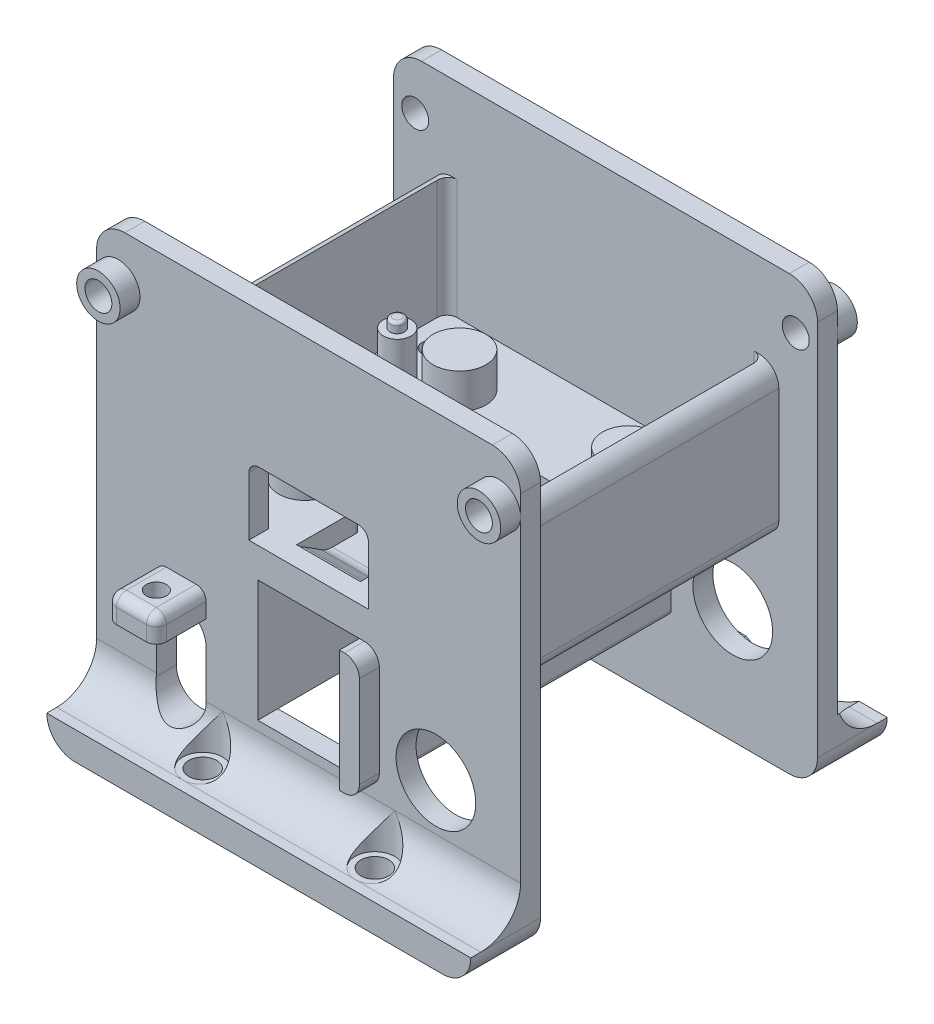
SolidWorks part; units mm, degrees
other "标注1"
sketch "草图55" plane through (-21.28, -20, 20.9) normal (0, 0, 1) x (1, 0, 0)
material "尼龙 101"
ref_plane "前视基准面" through (0, 0, 0) normal (0, 0, 1) x (1, 0, 0)
ref_plane "上视基准面" through (0, 0, 0) normal (0, 1, 0) x (1, 0, 0)
ref_plane "右视基准面" through (0, 0, 0) normal (1, 0, 0) x (0, 0, -1)
other "Configuration Table"
sketch "草图1" plane through (0, 0, 0) normal (0, 1, 0) x (1, 0, 0)
  line L1 (-15.9, 13.9) -> (15.9, 13.9)
  line L2 (-15.9, 13.9) -> (-15.9, -13.9)
  line L3 (-15.9, -13.9) -> (15.9, -13.9)
  line L4 (15.9, 13.9) -> (15.9, -13.9)
  line L5 (-15.9, 13.9) -> (15.9, -13.9) construction
  line L6 (-15.9, -13.9) -> (15.9, 13.9) construction
  point P0 (0, 0)
  dimension "D1" = 31.8
  dimension "D2" = 27.8
extrude "凸台-拉伸1" add sketch "草图1" along normal blind 3
sketch "草图2" plane through (0, 3, 0) normal (0, 1, 0) x (1, 0, 0)
  line L0 (0, 0) -> (0, 5.35) construction
  line L1 (-5.35, 5.35) -> (5.35, 5.35)
  line L2 (5.35, 5.35) -> (5.35, -7.55)
  line L3 (5.35, -7.55) -> (4.35, -7.55)
  line L4 (4.35, -7.55) -> (4.35, 4.35)
  line L5 (4.35, 4.35) -> (-4.35, 4.35)
  line L6 (-4.35, -7.55) -> (-4.35, 4.35)
  line L7 (-5.35, -7.55) -> (-4.35, -7.55)
  line L8 (-5.35, 5.35) -> (-5.35, -7.55)
  point P9 (0, 4.35)
  dimension "D1" = 8.7
  dimension "D2" = 11.9
  dimension "D3" = 4.35
  dimension "D4" = 1
  dimension "D5" = 1
extrude "凸台-拉伸2" add sketch "草图2" along normal blind 1.5
sketch "草图5" plane through (0, 3, 0) normal (0, 1, 0) x (1, 0, 0)
  line L0 (0, 13.9) -> (0, 0) construction
  line L1 (15.9, 13.9) -> (-15.9, 13.9) construction
  line L2 (0, 0) -> (15.9, 0) construction
  line L3 (15.9, -13.9) -> (15.9, 13.9) construction
  circle A0 centre (12.5, 5.5) radius 1.4
  circle A1 centre (12.5, -5.5) radius 1.4
  circle A2 centre (-12.5, -5.5) radius 1.4
  circle A3 centre (-12.5, 5.5) radius 1.4
  dimension "D1" = 2.8
  dimension "D2" = 25
  dimension "D3" = 11
extrude "凸台-拉伸3" add sketch "草图5" along normal blind 4.5
sketch "草图6" plane through (0, 7.5, 0) normal (0, 1, 0) x (1, 0, 0)
  circle A0 centre (-12.5, -5.5) radius 0.725
  circle A1 centre (-12.5, 5.5) radius 0.725
  circle A2 centre (12.5, 5.5) radius 0.725
  circle A3 centre (12.5, -5.5) radius 0.725
  dimension "D1" = 1.45
extrude "凸台-拉伸4" add sketch "草图6" along normal blind 1
sketch "草图7" plane through (0, 3, 0) normal (0, 1, 0) x (1, 0, 0)
  line L0 (0, 0) -> (0, 13.9) construction
  line L1 (15.9, 13.9) -> (-15.9, 13.9) construction
  line L2 (0, 0) -> (15.9, 0) construction
  line L3 (15.9, -13.9) -> (15.9, 13.9) construction
  circle A0 centre (13.5, 10) radius 1
  circle A1 centre (-13.5, 10) radius 1
  circle A2 centre (-13.5, -10) radius 1
  circle A3 centre (13.5, -10) radius 1
  dimension "D1" = 2
  dimension "D2" = 20
  dimension "D3" = 27
extrude "切除-拉伸1" cut sketch "草图7" against normal blind 10
sketch "草图8" plane through (0, 0, 0) normal (0, -1, 0) x (1, 0, 0)
  circle A0 centre (-13.5, 10) radius 2
  circle A1 centre (13.5, 10) radius 2
  circle A2 centre (13.5, -10) radius 2
  circle A3 centre (-13.5, -10) radius 2
  dimension "D1" = 4
extrude "切除-拉伸2" cut sketch "草图8" against normal blind 1
fillet "圆角1" radius 1 4 edges at (-15.9, 1.5, -13.9) (15.9, 1.5, -13.9) (-15.9, 1.5, 13.9) (15.9, 1.5, 13.9)
sketch "草图9" plane through (0, 3, 0) normal (0, 1, 0) x (1, 0, 0)
  line L0 (0, 13.9) -> (0, 0) construction
  line L1 (14.9, 13.9) -> (-14.9, 13.9) construction
  line L2 (0, 0) -> (15.9, 0) construction
  line L3 (15.9, -12.9) -> (15.9, 12.9) construction
  circle A0 centre (8.5, 7.75) radius 2.65
  circle A1 centre (-8.5, 7.75) radius 2.65
  circle A2 centre (-8.5, -7.75) radius 2.65
  circle A3 centre (8.5, -7.75) radius 2.65
  dimension "D1" = 17
  dimension "D2" = 15.5
  dimension "D3" = 5.3
extrude "凸台-拉伸5" add sketch "草图9" along normal blind 3.5
fillet "圆角2" radius 0.3 4 edges at (12.5, 8.5, -4.775) (12.5, 8.5, 6.225) (-12.5, 8.5, 6.225) (-12.5, 8.5, -4.775)
sketch "草图15" plane through (0, 3, 0) normal (0, 1, 0) x (1, 0, 0)
  line L0 (0, 0) -> (0, 13.9) construction
  line L1 (14.9, 13.9) -> (-14.9, 13.9) construction
  line L2 (-4.35, 4.35) -> (4.35, 4.35)
  line L3 (4.35, 4.35) -> (4.35, -7.55)
  line L4 (4.35, -7.55) -> (3.2, -7.55)
  line L5 (3.2, -7.55) -> (3.2, -13.9)
  line L6 (-14.9, -13.9) -> (14.9, -13.9) construction
  line L7 (3.2, -13.9) -> (-3.2, -13.9)
  line L8 (-3.2, -7.55) -> (-3.2, -13.9)
  line L9 (-4.35, -7.55) -> (-3.2, -7.55)
  line L10 (-4.35, 4.35) -> (-4.35, -7.55)
  line L11 (4.35, 4.35) -> (4.35, -7.55) construction
  point P14 (0, -13.9)
  point P17 (0, 4.35)
  dimension "D1" = 6.4
extrude "切除-拉伸8" cut sketch "草图15" against normal blind 2
sketch "草图17" plane through (0, 4.5, 0) normal (0, 1, 0) x (1, 0, 0)
  line L8 (-4.35, -7.55) -> (-4.35, 4.35)
  line L9 (-4.35, 4.35) -> (4.35, 4.35)
  line L10 (4.35, 4.35) -> (4.35, -7.55)
  line L11 (4.35, -7.55) -> (5.35, -7.55)
  line L12 (5.35, -7.55) -> (5.35, 5.35)
  line L13 (5.35, 5.35) -> (-5.35, 5.35)
  line L14 (-5.35, 5.35) -> (-5.35, -7.55)
  line L15 (-5.35, -7.55) -> (-4.35, -7.55)
  line L16 (-4.35, -7.55) -> (-4.35, 4.35)
  line L17 (-4.35, 4.35) -> (4.35, 4.35)
  line L18 (4.35, 4.35) -> (4.35, -7.55)
  line L19 (4.35, -7.55) -> (5.35, -7.55)
  line L20 (5.35, -7.55) -> (5.35, 5.35)
  line L21 (5.35, 5.35) -> (-5.35, 5.35)
  line L22 (-5.35, 5.35) -> (-5.35, -7.55)
  line L23 (-5.35, -7.55) -> (-4.35, -7.55)
  dimension "D1" = 0
extrude "切除-拉伸9" cut sketch "草图17" against normal blind 1.5
sketch "草图18" plane through (3.2, 0, 0) normal (-1, 0, 0) x (0, 0, 1)
  line L0 (13.9, 1) -> (10.9, 1)
  line L2 (13.9, 1) -> (13.9, 3) construction
  line L3 (13.9, 2.6) -> (13.9, 1)
  line L5 (13.9, 3) -> (13.9, 0) construction
  line L6 (13.9, 2.6) -> (13.4, 2.6)
  line L7 (13.4, 2.6) -> (10.9, 1)
  line L8 (13.9, 3) -> (12.9, 3) construction
  dimension "D1" = 3
  dimension "D2" = 0.4
  dimension "D3" = 0.5
extrude "凸台-拉伸6" add sketch "草图18" along normal up to surface (6.4 mm away) up to face at (-3.2, 2, 10.725)
fillet "圆角3" radius 2 1 edges at (0, 1, 10.9)
fillet "圆角5" radius 1 1 edges at (0, 2.6, 13.4)
fillet "圆角6" radius 0.4 2 edges at (3.2, 2, 7.55) (-3.2, 2, 7.55)
sketch "草图21" plane through (0, 0, 0) normal (0, -1, 0) x (1, 0, 0)
  line L0 (-14.9, 13.9) -> (14.9, 13.9) construction
  line L1 (-15.9, -12.9) -> (-15.9, 12.9) construction
  line L2 (14.9, -13.9) -> (-14.9, -13.9) construction
  line L3 (15.9, 12.9) -> (15.9, -12.9) construction
  line L4 (-14.9, 13.9) -> (14.9, 13.9)
  line L5 (-15.9, -12.9) -> (-15.9, 12.9)
  line L6 (14.9, -13.9) -> (-14.9, -13.9)
  line L7 (15.9, 12.9) -> (15.9, -12.9)
  line L9 (-17.4, 15.9) -> (17.4, 15.9)
  line L10 (-17.4, 15.9) -> (-17.4, -15.9)
  line L11 (-17.4, -15.9) -> (17.4, -15.9)
  line L12 (17.4, 15.9) -> (17.4, -15.9)
  arc A0 (15.9, 12.9) -> (14.9, 13.9) centre (14.9, 12.9) ccw construction
  arc A1 (-14.9, 13.9) -> (-15.9, 12.9) centre (-14.9, 12.9) ccw construction
  arc A2 (-15.9, -12.9) -> (-14.9, -13.9) centre (-14.9, -12.9) ccw construction
  arc A3 (14.9, -13.9) -> (15.9, -12.9) centre (14.9, -12.9) ccw construction
  arc A4 (15.9, 12.9) -> (14.9, 13.9) centre (14.9, 12.9) ccw
  arc A5 (-14.9, 13.9) -> (-15.9, 12.9) centre (-14.9, 12.9) ccw
  arc A6 (-15.9, -12.9) -> (-14.9, -13.9) centre (-14.9, -12.9) ccw
  arc A7 (14.9, -13.9) -> (15.9, -12.9) centre (14.9, -12.9) ccw
  dimension "D1" = 1.5
  dimension "D2" = 1.5
  dimension "D3" = 2
  dimension "D4" = 2
extrude "凸台-拉伸7" add sketch "草图21" against normal blind 15
sketch "草图22" plane through (0, 0, 15.9) normal (0, 0, 1) x (1, 0, 0)
  line L2 (-21.28, 0) -> (-21.28, 20.67)
  line L3 (-18.45, 23.5) -> (18.45, 23.5)
  line L4 (21.28, 0) -> (21.28, 20.67)
  line L5 (-21.28, 0) -> (21.28, 23.5) construction
  line L6 (-21.28, 23.5) -> (21.28, 0) construction
  line L7 (0, 0) -> (0, 23.5) construction
  line L10 (-21.28, 0) -> (-21.28, -17.17)
  line L11 (-18.45, -20) -> (18.45, -20)
  line L12 (21.28, 0) -> (21.28, -17.17)
  arc A0 (-21.28, 20.67) -> (-18.45, 23.5) centre (-18.45, 20.67) cw
  arc A1 (18.45, 23.5) -> (21.28, 20.67) centre (18.45, 20.67) cw
  arc A4 (18.45, -20) -> (21.28, -17.17) centre (18.45, -17.17) ccw
  arc A5 (-21.28, -17.17) -> (-18.45, -20) centre (-18.45, -17.17) ccw
  circle A9 centre (19.1, 18.67) radius 1.35
  circle A10 centre (-19.1, 18.67) radius 1.35
  point P4 (0, 11.75)
  point P22 (21.28, -20)
  dimension "D3" = 2.83
  dimension "D4" = 2.83
  dimension "D8" = 2.83
  dimension "D1" = 42.56
  dimension "D2" = 23.5
  dimension "D7" = 20
extrude "凸台-拉伸8" add sketch "草图22" against normal blind 2
sketch "草图24" plane through (0, 0, -15.9) normal (0, 0, -1) x (-1, 0, 0)
  line L5 (-18.45, -20) -> (18.45, -20)
  line L6 (-18.45, -20) -> (18.45, -20)
  line L21 (21.28, -17.17) -> (21.28, 20.67)
  line L22 (18.45, 23.5) -> (-18.45, 23.5)
  line L23 (-21.28, 20.67) -> (-21.28, -17.17)
  line L37 (21.28, -17.17) -> (21.28, 20.67)
  line L38 (18.45, 23.5) -> (-18.45, 23.5)
  line L39 (-21.28, 20.67) -> (-21.28, -17.17)
  arc A2 (21.28, 20.67) -> (18.45, 23.5) centre (18.45, 20.67) ccw
  arc A3 (-18.45, 23.5) -> (-21.28, 20.67) centre (-18.45, 20.67) ccw
  arc A4 (21.28, 20.67) -> (18.45, 23.5) centre (18.45, 20.67) ccw
  arc A5 (-18.45, 23.5) -> (-21.28, 20.67) centre (-18.45, 20.67) ccw
  circle A10 centre (19.1, 18.67) radius 1.35 construction
  circle A11 centre (-19.1, 18.67) radius 1.35 construction
  arc A12 (-21.28, -17.17) -> (-18.45, -20) centre (-18.45, -17.17) ccw
  arc A13 (-21.28, -17.17) -> (-18.45, -20) centre (-18.45, -17.17) ccw
  arc A14 (18.45, -20) -> (21.28, -17.17) centre (18.45, -17.17) ccw
  arc A15 (18.45, -20) -> (21.28, -17.17) centre (18.45, -17.17) ccw
  circle A16 centre (19.1, 18.67) radius 1.35
  circle A17 centre (-19.1, 18.67) radius 1.35
  dimension "D1" = 0
extrude "凸台-拉伸9" add sketch "草图24" against normal blind 2
sketch "草图25" plane through (0, 0, 15.9) normal (0, 0, 1) x (1, 0, 0)
  line L1 (-5, 9.85) -> (5, 9.85)
  line L2 (-6, 8.85) -> (-6, 3)
  line L4 (6, 8.85) -> (6, 3)
  line L5 (-6, 3) -> (6, 3)
  line L9 (-6, 3) -> (6, 9.85) construction
  arc A0 (5, 9.85) -> (6, 8.85) centre (5, 8.85) cw
  arc A1 (-5, 9.85) -> (-6, 8.85) centre (-5, 8.85) ccw
  point P5 (6, 9.85)
  point P8 (0, 6.425)
  point P9 (-6, 9.85)
  dimension "D2" = 1
  dimension "D1" = 12
extrude "切除-拉伸10" cut sketch "草图25" against normal blind 2
sketch "草图27" plane through (0, 0, 15.9) normal (0, 0, 1) x (1, 0, 0)
  line L0 (-5.1, 0) -> (5.1, -12.2) construction
  line L5 (-5.1, 0) -> (5.1, 0) construction
  line L16 (-17.4, 0) -> (17.4, 0) construction
  line L18 (-5.1, 0) -> (-5.1, -12.2)
  line L20 (5.1, 0) -> (5.1, -12.2)
  line L21 (-6.6, 0) -> (-6.6, -11.7)
  line L26 (6.6, 0) -> (6.6, -11.7)
  line L31 (-6.6, 0) -> (-5.1, 0)
  line L33 (-6.1, -12.2) -> (-5.1, -12.2)
  line L34 (-6.6, 1.5) -> (6.6, 1.5) construction
  line L35 (0, 0) -> (0, -4.0507) construction
  line L36 (6.6, 1.5) -> (6.6, -13.7) construction
  line L37 (-6.6, 1.5) -> (-6.6, -13.7) construction
  line L38 (5.1, 0) -> (6.6, 0)
  line L39 (-6.6, -13.7) -> (6.6, -13.7) construction
  line L40 (-5.1, -12.2) -> (5.1, -12.2) construction
  line L41 (5.1, -12.2) -> (6.1, -12.2)
  arc A4 (6.1, -12.2) -> (6.6, -11.7) centre (6.1, -11.7) ccw
  arc A5 (-6.6, -11.7) -> (-6.1, -12.2) centre (-6.1, -11.7) ccw
  point P6 (-2.5, 0)
  point P7 (6.9808, -17.5163)
  point P19 (6.6, -12.2)
  point P24 (0, -6.1)
  dimension "D4" = 0.5
  dimension "D1" = 10.2
  dimension "D2" = 12.2
  dimension "D3" = 1.5
extrude "凸台-拉伸10" add sketch "草图27" against normal up to surface (29.8 mm away) up to face at (0, 8.25, -13.9)
sketch "草图35" plane through (0, 0, 15.9) normal (0, 0, 1) x (1, 0, 0)
  line L1 (-5.1, 0) -> (5.1, 0)
  line L2 (-5.1, 0) -> (-5.1, -12.2)
  line L3 (-5.1, -12.2) -> (5.1, -12.2)
  line L4 (5.1, 0) -> (5.1, -12.2)
extrude "切除-拉伸14" cut sketch "草图35" against normal through all
sketch "草图43" plane through (0, 0, 15.9) normal (0, 0, 1) x (1, 0, 0)
  line L0 (-21.28, -17.17) -> (21.28, -17.17)
  line L1 (-18.45, -20) -> (18.45, -20) construction
  line L2 (-18.45, -20) -> (18.45, -20)
  arc A1 (18.45, -20) -> (21.28, -17.17) centre (18.45, -17.17) ccw construction
  arc A3 (-21.28, -17.17) -> (-18.45, -20) centre (-18.45, -17.17) ccw construction
  arc A4 (18.45, -20) -> (21.28, -17.17) centre (18.45, -17.17) ccw
  arc A5 (-21.28, -17.17) -> (-18.45, -20) centre (-18.45, -17.17) ccw
extrude "凸台-拉伸14" add sketch "草图43" along normal blind 5
sketch "草图44" plane through (-21.28, 0, 0) normal (-1, 0, 0) x (0, 0, 1)
  line L3 (15.9, -13.17) -> (15.9, -17.17)
  line L4 (15.9, -17.17) -> (19.9, -17.17)
  arc A0 (19.9, -17.17) -> (15.9, -13.17) centre (19.9, -13.17) cw
  point P8 (15.9, -17.17)
  dimension "D1" = 4
extrude "凸台-拉伸15" add sketch "草图44" against normal up to surface (42.56 mm away) up to face at (21.28, 1.75, 14.9)
sketch "草图45" plane through (0, 0, -15.9) normal (0, 0, -1) x (-1, 0, 0)
  line L0 (-18.45, -20) -> (18.45, -20) construction
  line L1 (-21.28, -17.17) -> (21.28, -17.17) construction
  line L2 (-18.45, -20) -> (18.45, -20)
  line L3 (-21.28, -17.17) -> (21.28, -17.17)
  arc A0 (-21.28, -17.17) -> (-18.45, -20) centre (-18.45, -17.17) ccw construction
  arc A1 (18.45, -20) -> (21.28, -17.17) centre (18.45, -17.17) ccw construction
  arc A2 (-21.28, -17.17) -> (-18.45, -20) centre (-18.45, -17.17) ccw
  arc A3 (18.45, -20) -> (21.28, -17.17) centre (18.45, -17.17) ccw
extrude "凸台-拉伸16" add sketch "草图45" along normal blind 5
sketch "草图46" plane through (21.28, 0, 0) normal (1, 0, 0) x (0, 0, -1)
  line L0 (15.9, -13.17) -> (15.9, -17.17)
  line L1 (15.9, -17.17) -> (19.9, -17.17)
  arc A0 (15.9, -13.17) -> (19.9, -17.17) centre (19.9, -13.17) ccw
  point P7 (15.9, -17.17)
  dimension "D1" = 4
extrude "凸台-拉伸17" add sketch "草图46" against normal up to surface (42.56 mm away) up to face at (-21.28, 1.75, -14.9)
sketch "草图36" plane through (0, 0, 15.9) normal (0, 0, 1) x (1, 0, 0)
  line L0 (-5.1, 0) -> (5.1, -12.2) construction
  line L1 (5.1, 0) -> (-5.1, -12.2) construction
  line L2 (-5.1, -12.2) -> (5.1, -12.2) construction
  line L3 (-5.1, 0) -> (-5.1, -12.2) construction
  line L6 (-5.1, -12.2) -> (-5.1, -13.2) construction
  line L7 (-5.1, -13.2) -> (22.8364, -13.2) construction
  line L8 (21.28, -13.17) -> (21.28, 20.67) construction
  line L10 (-15.28, -8.4815) -> (-15.28, -13.4815)
  line L12 (-10.28, -13.4815) -> (-10.28, -8.4815)
  circle A0 centre (0, -6.1) radius 4.5 construction
  circle A3 centre (12.78, -8.4815) radius 8.5 construction
  circle A6 centre (12.78, -8.4815) radius 5.75 construction
  circle A7 centre (12.78, -8.4815) radius 4
  arc A9 (-10.28, -8.4815) -> (-15.28, -8.4815) centre (-12.78, -8.4815) ccw
  arc A11 (-15.28, -13.4815) -> (-10.28, -13.4815) centre (-12.78, -13.4815) ccw
  point P11 (0, -6.1)
  dimension "D1" = 9
  dimension "D2" = 17
  dimension "D3" = 8
  dimension "D4" = 9
  dimension "D5" = 11.5
extrude "切除-拉伸15" cut sketch "草图36" against normal through all both and the other way through all
sketch "草图37" plane through (0, 0, 15.9) normal (0, 0, 1) x (1, 0, 0)
  line L0 (-15.28, -5.9815) -> (-15.28, -3.4815)
  line L1 (-15.28, -3.4815) -> (-10.28, -3.4815)
  line L2 (-10.28, -3.4815) -> (-10.28, -5.9815)
  line L3 (-15.28, -5.9815) -> (-10.28, -5.9815)
extrude "凸台-拉伸11" add sketch "草图37" along normal blind 5
sketch "草图38" plane through (0, 0, -15.9) normal (0, 0, -1) x (-1, 0, 0)
  line L0 (15.28, -3.4815) -> (15.28, -5.9815) construction
  line L1 (10.28, -5.9815) -> (10.28, -3.4815) construction
  line L2 (10.28, -3.4815) -> (15.28, -3.4815) construction
  line L3 (15.28, -3.4815) -> (15.28, -5.9815)
  line L4 (10.28, -5.9815) -> (10.28, -3.4815)
  line L5 (10.28, -3.4815) -> (15.28, -3.4815)
  line L6 (10.28, -5.9815) -> (15.28, -5.9815)
extrude "凸台-拉伸12" add sketch "草图38" along normal blind 5
fillet "圆角7" radius 1 2 edges at (-10.28, -4.7315, 20.9) (-15.28, -4.7315, 20.9)
fillet "圆角8" radius 1 2 edges at (-10.28, -4.7315, -20.9) (-15.28, -4.7315, -20.9)
sketch "草图41" plane through (0, 0, 15.9) normal (0, 0, 1) x (1, 0, 0)
  line L1 (5.1, 0) -> (5.6, 0)
  line L2 (5.1, 0) -> (5.1, -12.2)
  line L3 (5.1, -12.2) -> (5.6, -12.2)
  line L4 (7.1, -1.5) -> (7.1, -10.7)
  arc A0 (5.6, -12.2) -> (7.1, -10.7) centre (5.6, -10.7) ccw
  arc A1 (7.1, -1.5) -> (5.6, 0) centre (5.6, -1.5) ccw
  dimension "D1" = 1.5
  dimension "D2" = 2
extrude "凸台-拉伸13" add sketch "草图41" along normal blind 2
sketch "草图42" plane through (0, -3.4815, 0) normal (0, 1, 0) x (1, 0, 0)
  line L0 (-14.9871, 20.6071) -> (-10.28, 15.9) construction
  line L1 (-15.28, -15.9) -> (-10.5729, -20.6071) construction
  line L2 (-10.5729, 20.6071) -> (-15.28, 15.9) construction
  line L3 (-10.28, -15.9) -> (-14.9871, -20.6071) construction
  arc A0 (-14.28, 20.9) -> (-15.28, 19.9) centre (-14.28, 19.9) ccw construction
  arc A1 (-10.28, 19.9) -> (-11.28, 20.9) centre (-11.28, 19.9) ccw construction
  arc A2 (-11.28, -20.9) -> (-10.28, -19.9) centre (-11.28, -19.9) ccw construction
  arc A3 (-15.28, -19.9) -> (-14.28, -20.9) centre (-14.28, -19.9) ccw construction
  circle A4 centre (-12.78, -18.4) radius 1
  circle A5 centre (-12.78, 18.4) radius 1
  point P24 (-12.78, 18.4)
  point P25 (-12.78, -18.4)
  dimension "D1" = 2
  dimension "D2" = 2
sketch "草图49" plane through (0, -20, 0) normal (0, -1, 0) x (1, 0, 0)
  line L5 (8.64, 17.89) -> (-8.64, -17.89) construction
  line L6 (-8.64, 17.89) -> (8.64, 17.89) construction
  line L7 (-8.64, 17.89) -> (-8.64, -17.89) construction
  line L8 (-8.64, -17.89) -> (8.64, -17.89) construction
  line L9 (8.64, 17.89) -> (8.64, -17.89) construction
  circle A1 centre (-8.64, 17.89) radius 1.4
  circle A2 centre (8.64, 17.89) radius 1.4
  circle A3 centre (8.64, -17.89) radius 1.4
  circle A4 centre (-8.64, -17.89) radius 1.4
  point P6 (0, 0)
  dimension "D1" = 17.28
  dimension "D2" = 35.78
extrude "切除-拉伸17" cut sketch "草图49" against normal blind 6
sketch "草图51" plane through (0, 0, -15.9) normal (0, 0, -1) x (-1, 0, 0)
  circle A3 centre (-12.78, -8.4815) radius 10.3764
extrude "切除-拉伸18" cut sketch "草图51" along normal blind 6
sketch "草图52" plane through (0, -17.17, 0) normal (0, 1, 0) x (1, 0, 0)
  circle A3 centre (-8.64, -17.89) radius 1.99
  circle A4 centre (-8.64, 17.89) radius 1.99
  circle A6 centre (8.64, -17.89) radius 1.99
extrude "切除-拉伸20" cut sketch "草图52" along normal blind 4
fillet "圆角10" radius 1 5 edges at (-14.9871, -3.4815, 20.6071) (-12.78, -3.4815, 20.9) (-10.5729, -3.4815, 20.6071) (-10.28, -3.4815, 17.9) (-15.28, -3.4815, 17.9)
fillet "圆角12" radius 1 5 edges at (-15.28, -3.4815, -17.9) (-14.9871, -3.4815, -20.6071) (-12.78, -3.4815, -20.9) (-10.5729, -3.4815, -20.6071) (-10.28, -3.4815, -17.9)
extrude "切除-拉伸21" cut sketch "草图42" against normal blind 4
ref_plane "基准面7" through (0, 0, -6.3) normal (0, 0, -1) x (-1, 0, 0)
sketch "草图54" plane through (0, 0, -6.3) normal (0, 0, -1) x (-1, 0, 0)
  line L0 (-5.1, 0) -> (5.1, -12.2) construction
  line L1 (-5.1, 0) -> (5.1, 0)
  line L2 (-5.1, 0) -> (-5.1, -12.2)
  line L3 (-5.1, -12.2) -> (5.1, -12.2)
  line L4 (5.1, 0) -> (5.1, -12.2)
  line L5 (0, -1.6) -> (0, -10.6) construction
  circle A0 centre (0, -1.6) radius 0.8
  circle A1 centre (0, -10.6) radius 0.8
  circle A2 centre (0, -6.1) radius 1.8
  point P8 (0, -6.1)
  point P11 (0, -6.1)
  dimension "D1" = 9
  dimension "D2" = 0
  dimension "D3" = 0
extrude "凸台-拉伸18" add sketch "草图54" along normal blind 2
fillet "圆角13" radius 1.5 2 edges at (17.4, 0, 0) (-17.4, 0, 0)
sketch "草图56" plane through (0, 0, -15.9) normal (0, 0, -1) x (-1, 0, 0)
  circle A1 centre (19.1, 18.67) radius 1.35 construction
  circle A2 centre (19.1, 18.67) radius 1.35
  circle A3 centre (19.1, 18.67) radius 2.1725
  circle A4 centre (-19.1, 18.67) radius 1.35
  circle A5 centre (-19.1, 18.67) radius 2.18
extrude "凸台-拉伸19" add sketch "草图56" along normal blind 2
sketch "草图57" plane through (0, 0, 15.9) normal (0, 0, 1) x (1, 0, 0)
  circle A0 centre (-19.1, 18.67) radius 1.35
  circle A1 centre (-19.1, 18.67) radius 2.18
  circle A2 centre (19.1, 18.67) radius 1.3466
  circle A3 centre (19.1, 18.67) radius 2.18
extrude "凸台-拉伸20" add sketch "草图57" along normal blind 2
fillet "圆角14" radius 2 2 edges at (-17.4, 15, 0) (17.4, 15, 0)
